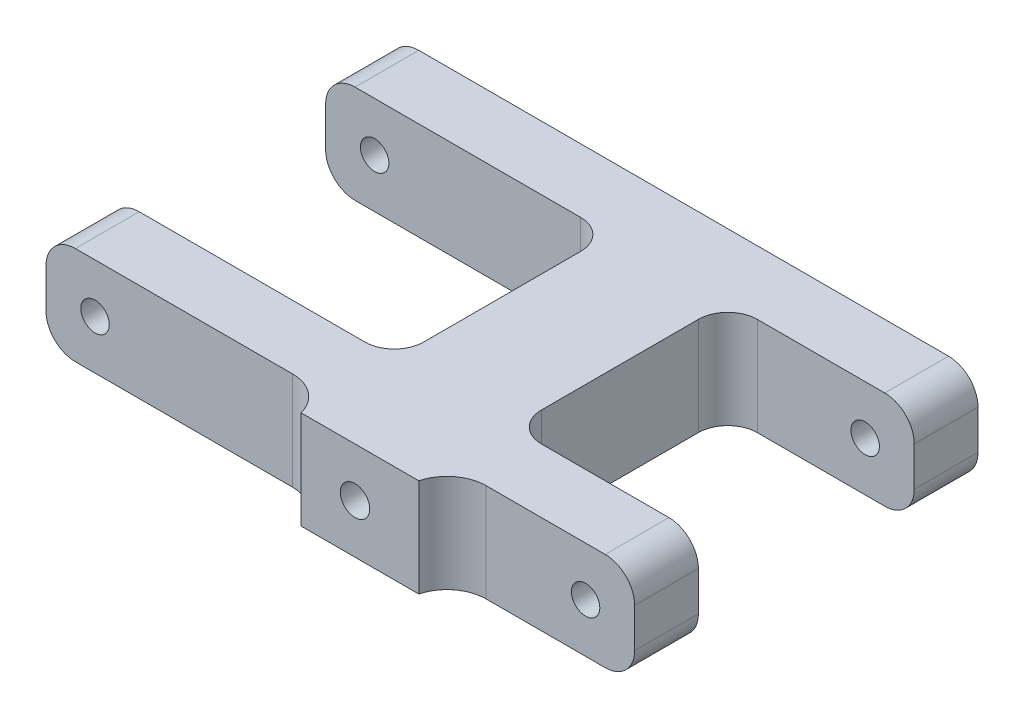
SolidWorks part; units mm, degrees
ref_plane "Front" through (0, 0, 0) normal (0, 0, 1) x (1, 0, 0)
ref_plane "Top" through (0, 0, 0) normal (0, 1, 0) x (1, 0, 0)
ref_plane "Right" through (0, 0, 0) normal (1, 0, 0) x (0, 0, -1)
sketch "Sketch1" plane through (0, 0, 0) normal (0, 1, 0) x (1, 0, 0)
  line L1 (0, 0) -> (60, 0)
  line L2 (0, 0) -> (0, -35)
  line L3 (0, -35) -> (60, -35)
  line L4 (60, 0) -> (60, -35)
  dimension "D1" = 35
  dimension "D2" = 60
extrude "Boss-Extrude1" add sketch "Sketch1" along normal blind 10
sketch "Sketch2" plane through (60, 0, 0) normal (1, 0, 0) x (0, 0, -1)
  line L0 (-35, 10) -> (0, 10) construction
  line L1 (-28.5, 10) -> (-6.5, 10)
  line L2 (-28.5, 10) -> (-28.5, 0)
  line L3 (-28.5, 0) -> (-6.5, 0)
  line L4 (-6.5, 10) -> (-6.5, 0)
  line L5 (-35, 0) -> (0, 0) construction
  line L6 (-35, 10) -> (-35, 0) construction
  line L7 (0, 10) -> (0, 0) construction
  dimension "D1" = 6.5
  dimension "D2" = 6.5
extrude "Cut-Extrude1" cut sketch "Sketch2" against normal blind 19
sketch "Sketch3" plane through (0, 0, 0) normal (-1, 0, 0) x (0, 0, 1)
  line L0 (0, 10) -> (35, 10) construction
  line L1 (6.5, 10) -> (28.5, 10)
  line L2 (6.5, 10) -> (6.5, 0)
  line L3 (6.5, 0) -> (28.5, 0)
  line L4 (28.5, 10) -> (28.5, 0)
  line L5 (0, 0) -> (35, 0) construction
  line L6 (35, 10) -> (35, 0) construction
  line L7 (0, 10) -> (0, 0) construction
  dimension "D1" = 6.5
  dimension "D2" = 6.5
extrude "Cut-Extrude2" cut sketch "Sketch3" against normal blind 29
sketch "Sketch5" plane through (0, 0, 35) normal (0, 0, 1) x (1, 0, 0)
  line L0 (0, 10) -> (60, 10) construction
  line L1 (0, 10) -> (0, 0) construction
  circle A0 centre (5, 5) radius 1.45
  circle A1 centre (55, 5) radius 1.45
  dimension "D1" = 2.9
  dimension "D2" = 5
  dimension "D3" = 5
  dimension "D4" = 2
extrude "Cut-Extrude4" cut sketch "Sketch5" against normal through all
fillet "Fillet1" radius 3 8 edges at (0, 0, 31.75) (0, 10, 31.75) (0, 0, 3.25) (0, 10, 3.25) (60, 10, 3.25) (60, 0, 3.25) (60, 0, 31.75) (60, 10, 31.75)
fillet "Fillet2" radius 3 4 edges at (41, 5, 28.5) (41, 5, 6.5) (29, 5, 28.5) (29, 5, 6.5)
sketch "Sketch7" plane through (0, 0, 35) normal (0, 0, 1) x (1, 0, 0)
  line L0 (3, 10) -> (57, 10) construction
  line L1 (29, 10) -> (41, 10)
  line L2 (29, 10) -> (29, 0)
  line L3 (29, 0) -> (41, 0)
  line L4 (41, 10) -> (41, 0)
  line L5 (3, 0) -> (57, 0) construction
  line L6 (60, 7) -> (60, 3) construction
  line L7 (0, 7) -> (0, 3) construction
  dimension "D1" = 19
  dimension "D2" = 29
extrude "Boss-Extrude2" add sketch "Sketch7" along normal blind 3
sketch "Sketch6" plane through (0, 0, 35) normal (0, 0, 1) x (1, 0, 0)
  line L0 (3, 0) -> (29, 0) construction
  line L2 (0, 7) -> (0, 3) construction
  circle A0 centre (34.5, 5) radius 1.5
  dimension "D1" = 3
  dimension "D2" = 5
  dimension "D3" = 34.5
extrude "Cut-Extrude5" cut sketch "Sketch6" against normal blind 15 and the other way blind 3
fillet "Fillet3" radius 4 2 edges at (41, 5, 35) (29, 5, 35)
